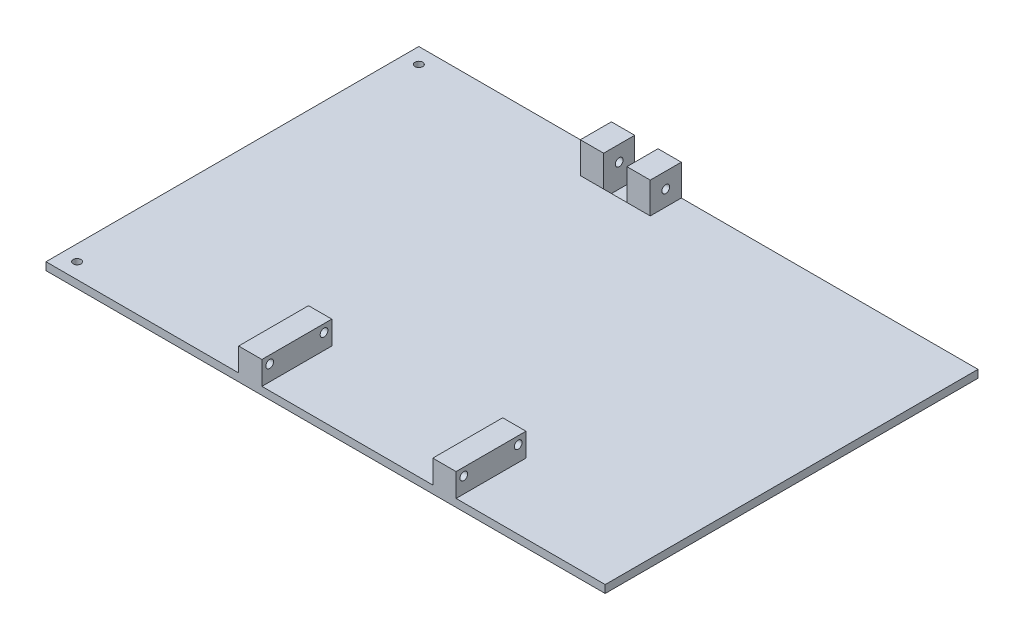
SolidWorks part; units mm, degrees
ref_plane "Front Plane" through (0, 0, 0) normal (0, 0, 1) x (1, 0, 0)
ref_plane "Top Plane" through (0, 0, 0) normal (0, 1, 0) x (1, 0, 0)
ref_plane "Right Plane" through (0, 0, 0) normal (1, 0, 0) x (0, 0, -1)
sketch "Sketch1" plane through (0, 0, 0) normal (0, 1, 0) x (1, 0, 0)
  line L1 (-228.6, -152.4) -> (228.6, -152.4)
  line L2 (-228.6, -152.4) -> (-228.6, 152.4)
  line L3 (-228.6, 152.4) -> (228.6, 152.4)
  line L4 (228.6, -152.4) -> (228.6, 152.4)
  line L5 (-228.6, -152.4) -> (228.6, 152.4) construction
  line L6 (-228.6, 152.4) -> (228.6, -152.4) construction
  point P0 (0, 0)
  dimension "D1" = 304.8
  dimension "D2" = 457.2
extrude "Boss-Extrude1" add sketch "Sketch1" along normal blind 6.35 contours L3 L4 L1 L2
sketch "Sketch2" plane through (0, 6.35, 0) normal (0, 1, 0) x (1, 0, 0)
  line L0 (-228.6, 0) -> (228.6, 0) construction
  line L1 (-228.6, -152.4) -> (-228.6, 152.4) construction
  line L2 (228.6, -152.4) -> (228.6, 152.4) construction
ref_plane "Plane2" through (81.28, 0, 0) normal (1, 0, 0) x (0, 0, -1)
sketch "Sketch5" plane through (81.28, 0, 0) normal (1, 0, 0) x (0, 0, -1)
  line L0 (0, 67.3066) -> (0, -85.5253) construction
  dimension "D1" = 0
sketch "Sketch6" plane through (0, 6.35, 0) normal (0, 1, 0) x (1, 0, 0)
  line L0 (81.28, -3.4925) -> (81.28, 3.4925) construction
  line L1 (87.63, -152.4) -> (106.68, -152.4)
  line L2 (87.63, -152.4) -> (87.63, -95.25)
  line L3 (87.63, -95.25) -> (106.68, -95.25)
  line L4 (106.68, -152.4) -> (106.68, -95.25)
  line L5 (-228.6, -152.4) -> (228.6, -152.4) construction
  line L7 (-52.07, -95.25) -> (-71.12, -95.25)
  line L8 (-52.07, -95.25) -> (-52.07, -152.4)
  line L9 (-52.07, -152.4) -> (-71.12, -152.4)
  line L10 (-71.12, -95.25) -> (-71.12, -152.4)
  dimension "D1" = 57.15
  dimension "D2" = 19.05
  dimension "D3" = 19.05
  dimension "D4" = 177.8
  dimension "D5" = 6.35
extrude "Boss-Extrude3" add sketch "Sketch6" along normal blind 19.05
sketch "Sketch7" plane through (106.68, 0, 0) normal (1, 0, 0) x (0, 0, -1)
  line L0 (-152.4, 6.35) -> (152.4, 6.35) construction
  line L1 (-152.4, 25.4) -> (-152.4, 6.35) construction
  line L2 (-95.25, 25.4) -> (-95.25, 6.35) construction
  circle A0 centre (-101.6, 19.05) radius 3.175
  circle A1 centre (-146.05, 19.05) radius 3.175
  dimension "D1" = 6.35
  dimension "D2" = 6.35
  dimension "D3" = 12.7
  dimension "D4" = 6.35
  dimension "D5" = 6.35
extrude "Cut-Extrude1" cut sketch "Sketch7" against normal through all
sketch "Sketch15" plane through (0, 6.35, 0) normal (0, 1, 0) x (1, 0, 0)
  line L0 (-228.6, -152.4) -> (-71.12, -152.4) construction
  line L1 (-228.6, -152.4) -> (-228.6, 152.4) construction
  line L2 (-320.2699, 0) -> (346.4461, 0) construction
  circle A0 centre (-215.9, -139.7) radius 3.175
  circle A1 centre (-215.9, 139.7) radius 3.175
  dimension "D1" = 6.35
  dimension "D2" = 12.7
  dimension "D3" = 12.7
extrude "Cut-Extrude3" cut sketch "Sketch15" against normal through all
sketch "Sketch16" plane through (0, 6.35, 0) normal (0, 1, 0) x (1, 0, 0)
  line L0 (-228.6, 152.4) -> (228.6, 152.4) construction
  line L1 (-71.12, 152.4) -> (-52.07, 152.4)
  line L2 (-71.12, 152.4) -> (-71.12, 127)
  line L3 (-71.12, 127) -> (-52.07, 127)
  line L4 (-52.07, 152.4) -> (-52.07, 127)
  line L5 (-71.12, -95.25) -> (-71.12, -152.4) construction
  line L7 (-33.02, 152.4) -> (-13.97, 152.4)
  line L8 (-33.02, 152.4) -> (-33.02, 127)
  line L9 (-33.02, 127) -> (-13.97, 127)
  line L10 (-13.97, 152.4) -> (-13.97, 127)
  dimension "D1" = 19.05
  dimension "D2" = 25.4
  dimension "D3" = 19.05
  dimension "D4" = 19.05
extrude "Boss-Extrude6" add sketch "Sketch16" along normal blind 25.4
sketch "Sketch17" plane through (-13.97, 0, 0) normal (1, 0, 0) x (0, 0, -1)
  line L0 (127, 31.75) -> (152.4, 31.75) construction
  line L1 (127, 31.75) -> (127, 6.35) construction
  circle A0 centre (139.7, 19.05) radius 3.175
  dimension "D1" = 6.35
  dimension "D2" = 12.7
  dimension "D3" = 12.7
extrude "Cut-Extrude4" cut sketch "Sketch17" against normal through all
sketch "Sketch18" plane through (0, 6.35, 0) normal (0, 1, 0) x (1, 0, 0)
  line L1 (-52.07, 152.4) -> (-33.02, 152.4)
  line L2 (-52.07, 152.4) -> (-52.07, 127)
  line L3 (-52.07, 127) -> (-33.02, 127)
  line L4 (-33.02, 152.4) -> (-33.02, 127)
extrude "Cut-Extrude5" cut sketch "Sketch18" against normal blind 6.35
sketch "Sketch20" plane through (0, 0, 0) normal (0, -1, 0) x (1, 0, 0)
  line L0 (-228.6, -152.4) -> (-52.07, -152.4) construction
  line L1 (-71.12, -152.4) -> (-13.97, -152.4)
  line L2 (-71.12, -152.4) -> (-71.12, -107.95)
  line L3 (-71.12, -107.95) -> (-13.97, -107.95)
  line L4 (-13.97, -152.4) -> (-13.97, -107.95)
  line L5 (-52.07, -152.4) -> (-52.07, -127) construction
  line L6 (-33.02, -127) -> (-33.02, -152.4) construction
  line L7 (-52.07, -127) -> (-33.02, -127) construction
  dimension "D1" = 19.05
  dimension "D2" = 19.05
  dimension "D3" = 19.05
extrude "Boss-Extrude10" add sketch "Sketch20" along normal blind 6.35
